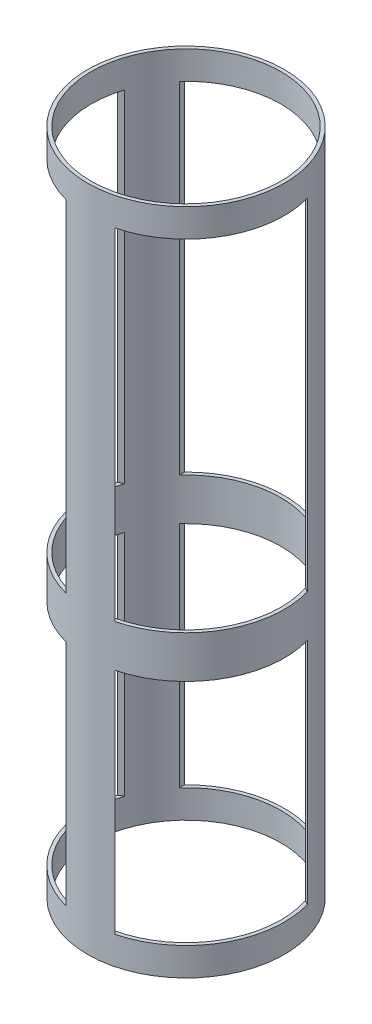
SolidWorks part; units mm, degrees
material "PVC Rigid"
ref_plane "Front Plane" through (0, 0, 0) normal (0, 0, 1) x (1, 0, 0)
ref_plane "Top Plane" through (0, 0, 0) normal (0, 1, 0) x (1, 0, 0)
ref_plane "Right Plane" through (0, 0, 0) normal (1, 0, 0) x (0, 0, -1)
sketch "Sketch1" plane through (0, 0, 0) normal (0, 1, 0) x (1, 0, 0)
  circle A0 centre (0, 0) radius 88.9
  circle A1 centre (0, 0) radius 85.725
  dimension "D1" = 177.8
  dimension "D2" = 171.45
extrude "Boss-Extrude1" add sketch "Sketch1" along normal mid plane 603.25
sketch "Sketch2" plane through (0, 0, 0) normal (0, 0, 1) x (1, 0, 0)
  line L0 (88.9, -301.625) -> (88.9, 301.625) construction
  line L5 (-88.9, -301.625) -> (88.9, -301.625) construction
  line L6 (63.5, -276.225) -> (-63.5, -276.225)
  line L7 (-88.9, 301.625) -> (-88.9, -301.625) construction
  line L9 (63.5, -276.225) -> (63.5, -69.723)
  line L10 (63.5, -69.723) -> (-63.5, -69.723)
  line L11 (-63.5, -276.225) -> (-63.5, -69.723)
  line L12 (85.725, 301.625) -> (-85.725, 301.625) construction
  line L13 (63.5, -31.623) -> (-63.5, -31.623)
  line L14 (63.5, -31.623) -> (63.5, 276.225)
  line L15 (63.5, 276.225) -> (-63.5, 276.225)
  line L16 (-63.5, -31.623) -> (-63.5, 276.225)
  dimension "D1" = 25.4
  dimension "D2" = 25.4
  dimension "D3" = 25.4
  dimension "D4" = 231.902
  dimension "D5" = 25.4
  dimension "D6" = 38.1
extrude "Cut-Extrude1" cut sketch "Sketch2" against normal up to surface (62.217 mm away) up to face at (0, 301.625, 88.9)
pattern_circular "CirPattern1" count 3 over 360 about axis through (0, 301.625, 0) along (0, -1, 0) of "Cut-Extrude1"
ref_plane "Plane1" through (0, 0, 88.9) normal (0, 0, 1) x (1, 0, 0)
sketch "Sketch3" plane through (0, 0, 88.9) normal (0, 0, 1) x (1, 0, 0)
  line L0 (0, -97.79) -> (0, 97.79) construction
  line L1 (88.9, 301.625) -> (-88.9, 301.625) construction
  circle A0 centre (0, 295.275) radius 1.4351
  dimension "D1" = 2.8702
  dimension "D2" = 6.35
extrude "Cut-Extrude2" [suppressed] cut sketch "Sketch3" against normal blind 25.908
pattern_circular "CirPattern2" [suppressed] count 12 over 360 of bodies 104
mirror "Mirror1" [suppressed] about plane through (0, 0, 0) normal (0, 1, 0)
sketch "Sketch4" [suppressed] plane through (0, 0, 88.9) normal (0, 0, 1) x (1, 0, 0)
  line L0 (0, -97.79) -> (0, 97.79) construction
  circle A0 centre (0, -225.425) radius 1.4351
  circle A1 centre (0, -212.725) radius 1.4351
  circle A2 centre (0, -295.275) radius 1.4351 construction
  circle A3 centre (0, -149.225) radius 1.4351
  circle A4 centre (0, -136.525) radius 1.4351
  dimension "D1" = 69.85
  dimension "D2" = 2.8702
  dimension "D3" = 12.7
  dimension "D4" = 2.8702
  dimension "D5" = 63.5
  dimension "D6" = 12.7
  dimension "D7" = 2.8702
  dimension "D8" = 2.8702
extrude "Cut-Extrude3" [suppressed] cut sketch "Sketch4" against normal blind 34.798
pattern_circular "CirPattern3" [suppressed] count 3 over 360 reverse direction yes of bodies 107
sketch "Sketch5" [suppressed] plane through (0, 0, 88.9) normal (0, 0, 1) x (1, 0, 0)
  line L0 (0, -97.79) -> (0, 97.79) construction
  line L1 (-22.1315, -31.623) -> (-88.9, -31.623) construction
  line L2 (-88.9, -69.723) -> (-22.1315, -69.723) construction
  line L3 (88.9, -31.623) -> (22.1315, -31.623) construction
  circle A0 centre (0, -50.673) radius 1.4351
  circle A1 centre (0, 73.025) radius 1.4351
  circle A2 centre (0, 177.927) radius 1.4351
  circle A3 centre (0, 295.275) radius 1.4351 construction
  circle A4 centre (0, -37.973) radius 1.4351
  circle A5 centre (0, -63.373) radius 1.4351
  dimension "D1" = 2.8702
  dimension "D3" = 117.348
  dimension "D5" = 2.8702
  dimension "D6" = 2.8702
  dimension "D4" = 123.698
  dimension "D7" = 2.8702
  dimension "D8" = 2.8702
  dimension "D9" = 6.35
  dimension "D10" = 6.35
  dimension "D2" = 19.05
extrude "Cut-Extrude4" [suppressed] cut sketch "Sketch5" against normal blind 87.63
pattern_circular "CirPattern4" [suppressed] count 12 over 360 reverse direction yes of bodies 109
